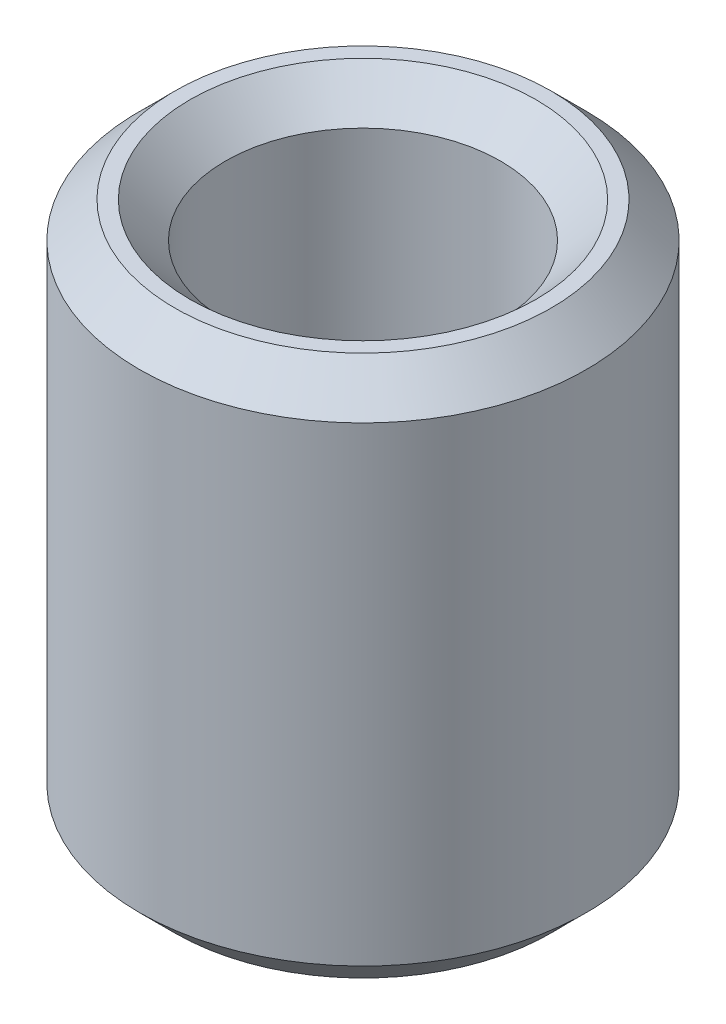
SolidWorks part; units mm, degrees
ref_plane "Front Plane" through (0, 0, 0) normal (0, 0, 1) x (1, 0, 0)
ref_plane "Top Plane" through (0, 0, 0) normal (0, 1, 0) x (1, 0, 0)
ref_plane "Right Plane" through (0, 0, 0) normal (1, 0, 0) x (0, 0, -1)
sketch "Sketch1" plane through (0, 0, 0) normal (0, 1, 0) x (1, 0, 0)
  circle A0 centre (0, 0) radius 22.5
  dimension "SLEEVE_OD" = 45
extrude "Boss-Extrude1" add sketch "Sketch1" along normal blind 54.4718
sketch "Sketch2" plane through (0, 0, 0) normal (0, 1, 0) x (1, 0, 0)
  circle A0 centre (0, 0) radius 13.8472
  dimension "BORE_D" = 27.6944
extrude "Cut-Extrude1" cut sketch "Sketch2" along normal through all
chamfer "Chamfer1" distance 3.5654 angle 45 4 edges at (0, 54.4718, 13.8472) (0, 0, 13.8472) (0, 0, 22.5) (0, 54.4718, 22.5)
